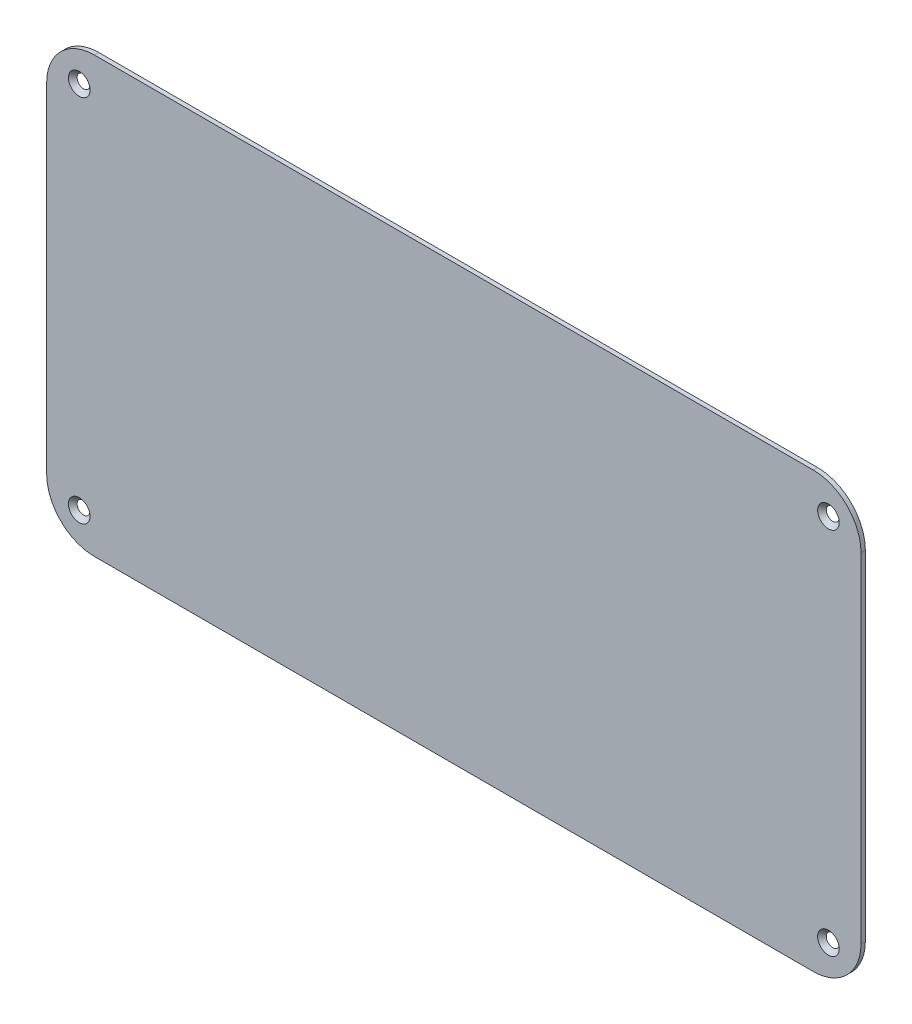
SolidWorks part; units mm, degrees
material "7079 Alloy"
ref_plane "Front" through (0, 0, 0) normal (0, 0, 1) x (1, 0, 0)
ref_plane "Top" through (0, 0, 0) normal (0, 1, 0) x (1, 0, 0)
ref_plane "Right" through (0, 0, 0) normal (1, 0, 0) x (0, 0, -1)
sketch "Sketch1" plane through (0, 0, 0) normal (0, 0, 1) x (1, 0, 0)
  line L0 (187.5, -100) -> (-187.5, 100) construction
  line L1 (-165.5, 100) -> (165.5, 100)
  line L2 (-187.5, 78) -> (-187.5, -78)
  line L3 (-165.5, -100) -> (165.5, -100)
  line L4 (187.5, 78) -> (187.5, -78)
  arc A0 (165.5, -100) -> (187.5, -78) centre (165.5, -78) ccw
  arc A1 (165.5, 100) -> (187.5, 78) centre (165.5, 78) cw
  arc A2 (-187.5, 78) -> (-165.5, 100) centre (-165.5, 78) cw
  arc A3 (-165.5, -100) -> (-187.5, -78) centre (-165.5, -78) cw
  point P10 (187.5, 100)
  point P16 (-187.5, -100)
  dimension "D3" = 22
  dimension "D1" = 375
  dimension "D2" = 200
sheet metal parameters "Sheet-Metal1" thickness 2 parameters "D1"=0.7366
base flange "Base-Flange1" sketch "Sketch1" thickness 2 reverse thickness direction yes parameters "D1"=0.7366
sketch "Sketch8" plane through (0, 0, 2) normal (0, 0, 1) x (1, 0, 0)
  line L0 (-165.5, -100) -> (165.5, -100) construction
  line L1 (-187.5, 78) -> (-187.5, -78) construction
  circle A0 centre (-147.5, -75) radius 1.75
  circle A1 centre (-134.5, -75) radius 1.75
  dimension "D1" = 3.5
  dimension "D2" = 3.5
  dimension "D4" = 40
  dimension "D5" = 53
  dimension "D3" = 25
extrude "Cut-Extrude11" [suppressed] cut sketch "Sketch8" against normal through all normal cut yes
sketch "Esboço7" plane through (0, 0, 0) normal (0, 0, -1) x (-1, 0, 0)
  line L0 (-187.5, -78) -> (-187.5, 78) construction
  line L3 (-165.5, 100) -> (165.5, 100) construction
  line L5 (187.5, 78) -> (187.5, -78) construction
  line L8 (165.5, -100) -> (-165.5, -100) construction
  circle A0 centre (-172.5, 85) radius 1.5
  circle A1 centre (172.5, 85) radius 1.5
  circle A2 centre (-172.5, -85) radius 1.5
  circle A3 centre (172.5, -85) radius 1.5
  dimension "D1" = 3
  dimension "D2" = 3
  dimension "D3" = 3
  dimension "D4" = 3
  dimension "D5" = 15
  dimension "D6" = 15
  dimension "D7" = 15
  dimension "D8" = 15
extrude "Corte-extrusão1" cut sketch "Esboço7" against normal through all contours A0 | A2 | A3 | A1 normal cut yes
hole_wizard "Escareado para parafuso Allen sextavado escareado de M41" positions "3DSketch3" profile "Esboço9" countersink size "M4" standard "ISO" end condition through all
sketch3d "3DSketch3"
  line L0 (-172.5, 85, 2) -> (-172.5, 85, 0) construction
  line L1 (-172.5, -85, 2) -> (-172.5, -85, 0) construction
  line L2 (172.5, 85, 2) -> (172.5, 85, 0) construction
  line L3 (172.5, -85, 2) -> (172.5, -85, 0) construction
  point P0 (-172.5, 85, 2)
  point P4 (-172.5, -85, 2)
  point P8 (172.5, 85, 2)
  point P12 (172.5, -85, 2)
sketch "Esboço9" plane through (-172.5, 85, 2) normal (1, 0, 0) x (0, -1, 0)
  line L0 (0, 0) -> (0, 2)
  line L1 (0, 2) -> (2.15, 2)
  line L2 (2.15, 2) -> (2.15, 2.83)
  line L3 (2.15, 2.83) -> (4.98, 0)
  line L5 (4.98, 0) -> (0, 0)
  line L6 (-2.15, 2.83) -> (-4.98, 0) construction
  line L11 (0, -6.35) -> (0, 107.95) construction
  dimension "Thru Hole Dia." = 4.3
  dimension "Thru Hole Depth" = 2
  dimension "Near C'Sink Dia." = 9.96
  dimension "Near C'Sink Angle" = 90
flat pattern "Flat-Pattern1" [suppressed]
sketch "Bend-Lines1" plane through (0, 0, 0) normal (0, 1, 0) x (-1, 0, 0)
